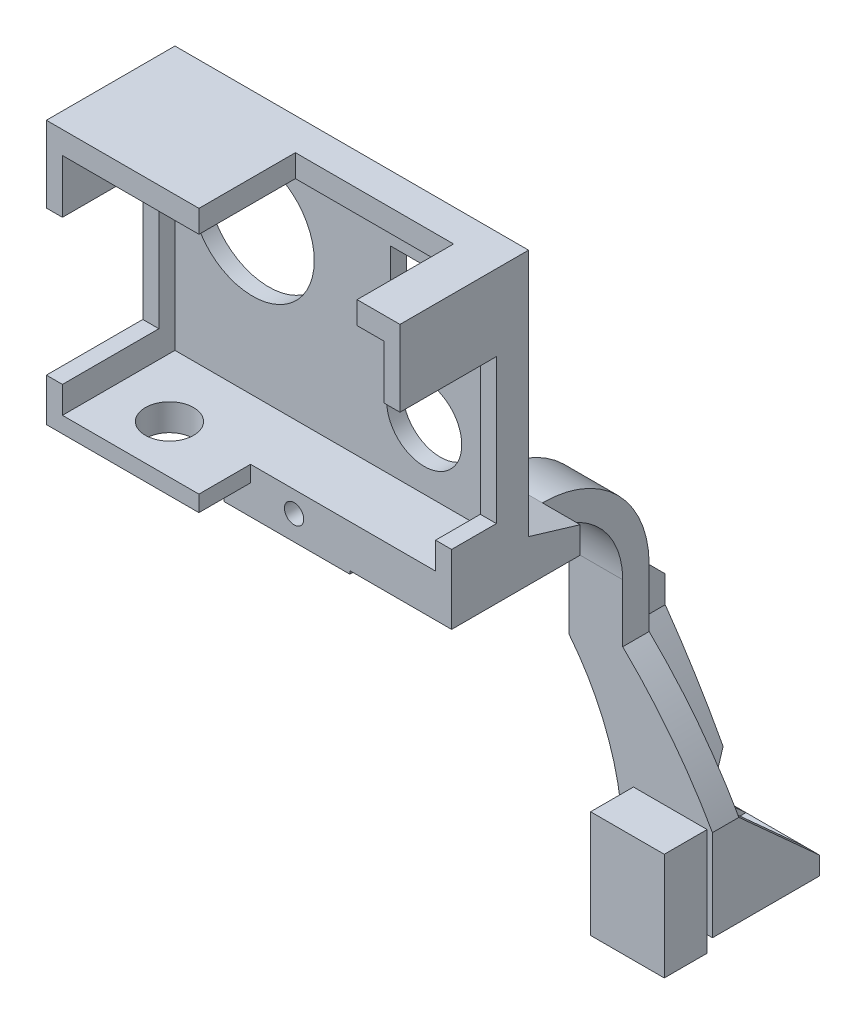
SolidWorks part; units mm, degrees
ref_plane "Plano frontal" through (0, 0, 0) normal (0, 0, 1) x (1, 0, 0)
ref_plane "Plano superior" through (0, 0, 0) normal (0, 1, 0) x (1, 0, 0)
ref_plane "Plano direito" through (0, 0, 0) normal (1, 0, 0) x (0, 0, -1)
sketch "Esboço1" plane through (0, 0, 0) normal (0, 0, 1) x (1, 0, 0)
  line L1 (0, 0) -> (-14.7, 0)
  line L3 (4.3, -61.4) -> (-14.7, -61.4)
  line L4 (-14.7, 0) -> (-14.7, -61.4)
  line L5 (0, 0) -> (4.3, -39.4)
  line L6 (4.3, -39.4) -> (4.3, -61.4)
  dimension "D1" = 14.7
  dimension "D2" = 19
  dimension "D3" = 22
  dimension "D4" = 39.4
extrude "Ressalto-extrusão1" add sketch "Esboço1" along normal blind 4.93
sketch "Esboço2" plane through (-14.7, 0, 0) normal (-1, 0, 0) x (0, 0, 1)
  line L0 (0, 0) -> (0, -61.4) construction
  line L1 (-6.1, 6.1) -> (-6.1, 11.03) construction
  line L3 (0, 0) -> (4.93, 0)
  line L4 (-6.1, 6.1) -> (-30.1, 6.1)
  line L5 (-30.1, 6.1) -> (-30.1, 11.03)
  line L6 (-30.1, 11.03) -> (-6.1, 11.03)
  arc A0 (0, 0) -> (-6.1, 6.1) centre (-6.1, 0) ccw
  arc A1 (4.93, 0) -> (-6.1, 11.03) centre (-6.1, 0) ccw
  dimension "D1" = 12.2
  dimension "D2" = 24
extrude "Ressalto-extrusão2" add sketch "Esboço2" against normal up to vertex (14.7 mm away) up to point (0, 0, 4.93)
ref_plane "Plano1" through (-12.76, 0, 0) normal (-1, 0, 0) x (0, 0, 1)
sketch "Esboço4" plane through (-12.76, 0, 0) normal (-1, 0, 0) x (0, 0, 1)
  line L0 (-30.1, 11.03) -> (-30.1, 6.1) construction
  line L1 (-30.1, 6.1) -> (-6.1, 6.1) construction
  line L2 (-6.1, 11.03) -> (-30.1, 11.03) construction
  line L3 (-45.1, -8.9) -> (-50.03, -8.9) construction
  line L4 (-30.1, 11.03) -> (-30.1, 6.1)
  line L5 (-45.1, -8.9) -> (-45.1, -61.4)
  line L6 (-45.1, -61.4) -> (-50.03, -61.4)
  line L7 (-50.03, -61.4) -> (-50.03, -8.9)
  line L8 (4.93, -61.4) -> (0, -61.4) construction
  arc A0 (-30.1, 6.1) -> (-45.1, -8.9) centre (-30.1, -8.9) ccw
  arc A1 (-30.1, 11.03) -> (-50.03, -8.9) centre (-30.1, -8.9) ccw
  dimension "D1" = 30
extrude "Ressalto-extrusão3" add sketch "Esboço4" against normal blind 10
sketch "Esboço5" plane through (0, 0, -50.03) normal (0, 0, -1) x (-1, 0, 0)
  line L0 (2.76, -8.9) -> (2.76, -61.4) construction
  line L1 (2.76, -19.73) -> (-13.99, -19.73)
  line L2 (2.76, -19.73) -> (2.76, -61.4)
  line L3 (2.76, -61.4) -> (-13.99, -61.4)
  line L4 (-13.99, -19.73) -> (-13.99, -61.4)
  line L5 (2.76, -61.4) -> (12.76, -61.4) construction
  dimension "D1" = 41.67
  dimension "D2" = 16.75
extrude "Ressalto-extrusão4" add sketch "Esboço5" against normal up to surface (4.93 mm away) up to face at (-7.76, -35.15, -45.1)
sketch "Esboço6" plane through (0, 0, -50.03) normal (0, 0, -1) x (-1, 0, 0)
  line L0 (2.76, -61.4) -> (2.76, -51.4) construction
  line L1 (12.76, -8.9) -> (12.76, -61.4) construction
  line L2 (2.76, -19.73) -> (2.76, -61.4) construction
  line L3 (-13.99, -61.4) -> (12.76, -61.4) construction
  line L4 (2.76, -19.73) -> (12.76, -19.73) construction
  line L7 (12.76, -61.4) -> (2.76, -61.4)
  line L8 (2.76, -61.4) -> (2.76, -51.4)
  line L9 (-13.99, -61.4) -> (-13.99, -41.4) construction
  line L10 (-13.99, -19.73) -> (-13.99, -61.4) construction
  line L11 (-13.99, -41.4) -> (-13.99, -19.73)
  line L12 (-13.99, -19.73) -> (2.76, -19.73)
  line L13 (12.76, -19.73) -> (12.76, -22.73)
  line L14 (12.76, -22.73) -> (12.76, -61.4)
  arc A1 (2.76, -19.73) -> (-13.99, -41.4) centre (69.0675, -88.2914) ccw
  arc A2 (12.76, -22.73) -> (2.76, -51.4) centre (48.675, -51.336) ccw
  dimension "D2" = 91.83
  dimension "D4" = 190.76
  dimension "D1" = 10
  dimension "D3" = 20
  dimension "D5" = 3
extrude "Corte-extrusão1" cut sketch "Esboço6" against normal up to next contours L14 L7 L8 A2 | L12 A1 L11
sketch "Esboço7" plane through (-2.76, 0, 0) normal (-1, 0, 0) x (0, 0, 1)
  line L0 (-50.03, -61.4) -> (-65.1, -61.4)
  line L1 (-65.1, -61.4) -> (-65.1, -55.04)
  line L2 (-65.1, -55.04) -> (-50.03, -41.4)
  line L4 (-50.03, -41.4) -> (-50.03, -61.4)
  line L5 (-45.1, -61.4) -> (-45.1, -51.4) construction
  dimension "D1" = 6.36
  dimension "D2" = 20
  dimension "D3" = 20
extrude "Ressalto-extrusão5" add sketch "Esboço7" against normal up to surface (16.75 mm away) contours L4 L0 L1 L2 up to face at (13.99, -51.4, -47.565)
sketch "Esboço8" plane through (-14.7, 0, 0) normal (-1, 0, 0) x (0, 0, 1)
  line L0 (4.93, -61.4) -> (20, -61.4)
  line L1 (20, -61.4) -> (20, -55.04)
  line L2 (20, -55.04) -> (4.93, -39.4)
  line L3 (4.93, 0) -> (4.93, -61.4) construction
  line L4 (0, 0) -> (0, -61.4) construction
  line L5 (4.93, -39.4) -> (4.93, -61.4)
  dimension "D1" = 20
  dimension "D2" = 6.36
  dimension "D3" = 22
extrude "Ressalto-extrusão6" add sketch "Esboço8" against normal up to surface (19 mm away) contours L5 L0 L1 L2 up to face at (4.3, -50.4, 2.465)
sketch "Esboço9" plane through (0, 0, -50.03) normal (0, 0, -1) x (-1, 0, 0)
  line L0 (-13.99, -41.4) -> (2.76, -41.4) construction
  line L1 (-10.99, -41.4) -> (-0.24, -41.4)
  line L2 (-10.99, -41.4) -> (-10.99, -55.04)
  line L3 (-10.99, -55.04) -> (-0.24, -55.04)
  line L4 (-0.24, -41.4) -> (-0.24, -55.04)
  line L5 (-13.99, -55.04) -> (2.76, -55.04) construction
  point P9 (-5.615, -41.4)
  point P10 (-5.615, -41.4)
  dimension "D1" = 10.75
extrude "Corte-extrusão2" cut sketch "Esboço9" along normal up to next
sketch "Esboço10" plane through (0, 0, 4.93) normal (0, 0, 1) x (1, 0, 0)
  line L0 (4.3, -39.4) -> (-14.7, -39.4) construction
  line L1 (-11.7, -39.4) -> (1.3, -39.4)
  line L2 (-11.7, -39.4) -> (-11.7, -55.04)
  line L3 (-11.7, -55.04) -> (1.3, -55.04)
  line L4 (1.3, -39.4) -> (1.3, -55.04)
  line L5 (4.3, -55.04) -> (-14.7, -55.04) construction
  point P9 (-5.2, -39.4)
  point P10 (-5.2, -39.4)
  dimension "D1" = 13
extrude "Corte-extrusão3" cut sketch "Esboço10" along normal up to next
sketch "Esboço11" plane through (0, -61.4, 0) normal (0, -1, 0) x (1, 0, 0)
  line L0 (13.99, -45.1) -> (-2.76, -45.1) construction
  line L1 (-0.76, -45.1) -> (12.99, -45.1)
  line L2 (-0.76, -45.1) -> (-0.76, -37.1)
  line L3 (-0.76, -37.1) -> (12.99, -37.1)
  line L4 (12.99, -45.1) -> (12.99, -37.1)
  line L5 (13.99, -45.1) -> (13.99, -65.1) construction
  dimension "D1" = 13.75
  dimension "D2" = 8
  dimension "D3" = 1
extrude "Ressalto-extrusão7" add sketch "Esboço11" against normal blind 20
sketch "Esboço12" plane through (0, 0, 4.93) normal (0, 0, 1) x (1, 0, 0)
  line L0 (0, 0) -> (-14.7, 0) construction
  line L1 (-10.35, 0) -> (-4.35, 0)
  line L2 (-10.35, 0) -> (-10.35, -39.4)
  line L3 (-10.35, -39.4) -> (-4.35, -39.4)
  line L4 (-4.35, 0) -> (-4.35, -39.4)
  line L5 (-11.7, -39.4) -> (-14.7, -39.4) construction
  point P9 (-7.35, 0)
  point P10 (-7.35, 0)
  dimension "D1" = 6
extrude "Ressalto-extrusão8" add sketch "Esboço12" along normal blind 5
sketch "Esboço13" plane through (0, 0, -50.03) normal (0, 0, -1) x (-1, 0, 0)
  line L0 (10.76, -8.9) -> (4.76, -8.9)
  line L1 (2.76, -8.9) -> (12.76, -8.9) construction
  line L2 (10.76, -8.9) -> (10.76, -19.73)
  line L3 (4.76, -8.9) -> (4.76, -18.9)
  line L4 (-8.615, -41.4) -> (-2.615, -41.4)
  line L5 (-10.99, -55.04) -> (-0.24, -55.04) construction
  line L6 (-13.99, -41.4) -> (-10.99, -41.4) construction
  arc A2 (10.76, -19.73) -> (-2.615, -41.4) centre (142.496, -116.0017) ccw
  arc A3 (4.76, -18.9) -> (-8.615, -41.4) centre (142.496, -116.0017) ccw
  point P5 (7.76, -8.9)
  point P6 (7.76, -8.9)
  point P13 (-5.615, -55.04)
  point P14 (-5.615, -41.4)
  dimension "D1" = 6
  dimension "D2" = 6
  dimension "D3" = 10
  dimension "D4" = 10.83
extrude "Ressalto-extrusão9" add sketch "Esboço13" along normal blind 5
chamfer "Chanfro1" distance 5 angle 45 2 edges at (-7.76, -8.9, -55.03) (5.615, -41.4, -55.03)
chamfer "Chanfro2" distance 5 angle 45 2 edges at (-7.35, -39.4, 9.93) (-7.35, 0, 9.93)
sketch "Esboço14" plane through (0, -55.04, 0) normal (0, 1, 0) x (1, 0, 0)
  line L0 (1.3, -20) -> (-11.7, -20) construction
  line L1 (10.99, 65.1) -> (0.24, 65.1) construction
  line L2 (1.3, -20) -> (1.3, -4.93) construction
  circle A0 centre (-5.2, -12.465) radius 1.6
  circle A1 centre (5.615, 57.56) radius 1.6
  point P4 (-5.2, -20)
  point P9 (5.615, 65.1)
  point P13 (1.3, -12.465)
  dimension "D1" = 3.2
  dimension "D2" = 7.54
extrude "Corte-extrusão4" cut sketch "Esboço14" against normal up to next
sketch "Esboço15" plane through (0, 11.03, 0) normal (0, 1, 0) x (1, 0, 0)
  line L0 (0, 30.1) -> (-2.76, 30.1) construction
  line L1 (-14.7, 6.1) -> (4.3, 6.1)
  line L2 (-14.7, 6.1) -> (-14.7, 30.1)
  line L3 (-14.7, 30.1) -> (4.3, 30.1)
  line L4 (4.3, 6.1) -> (4.3, 30.1)
  dimension "D1" = 19
extrude "Ressalto-extrusão10" add sketch "Esboço15" along normal blind 3 and the other way up to surface (4.93 mm away) other way up to face at (-7.4867, 6.1, -22.1)
sketch "Esboço16" plane through (0, 14.03, 0) normal (0, 1, 0) x (1, 0, 0)
  line L0 (4.3, 6.1) -> (4.3, 20.46) construction
  line L1 (4.3, 6.1) -> (4.3, 30.1) construction
  line L3 (4.3, 20.46) -> (-61.7, 20.46)
  line L4 (4.3, 20.46) -> (4.3, 17.46)
  line L5 (4.3, 17.46) -> (-61.7, 17.46)
  line L6 (-61.7, 20.46) -> (-61.7, 17.46)
  dimension "D1" = 3
  dimension "D2" = 14.36
  dimension "D3" = 66
extrude "Ressalto-extrusão11" add sketch "Esboço16" along normal blind 46.2 and the other way blind 3
sketch "Esboço17" plane through (0, 0, -17.46) normal (0, 0, 1) x (1, 0, 0)
  line L0 (-61.7, 60.23) -> (-33.22, 60.23)
  line L1 (-61.7, 60.23) -> (4.3, 60.23) construction
  line L2 (-33.22, 60.23) -> (-33.22, 56.03)
  line L3 (-33.22, 56.03) -> (-58.7, 56.03)
  line L4 (-58.7, 56.03) -> (-58.7, 46.03)
  line L5 (-58.7, 46.03) -> (-61.7, 46.03)
  line L6 (-61.7, 11.03) -> (-61.7, 60.23) construction
  line L7 (-61.7, 46.03) -> (-61.7, 60.23)
  line L15 (-61.7, 11.03) -> (-61.7, 19.03)
  line L16 (-61.7, 19.03) -> (-58.7, 19.03)
  line L17 (-58.7, 19.03) -> (-58.7, 14.03)
  line L18 (-58.7, 14.03) -> (-33.23, 14.03)
  line L19 (-33.23, 14.03) -> (-33.23, 11.03)
  line L20 (-61.7, 11.03) -> (-14.7, 11.03) construction
  line L21 (-33.23, 11.03) -> (-61.7, 11.03)
  line L22 (4.3, 60.23) -> (4.3, 46.03)
  line L23 (4.3, 14.03) -> (4.3, 60.23) construction
  line L24 (4.3, 60.23) -> (-3.7, 60.23)
  line L25 (-3.7, 60.23) -> (-3.7, 56.03)
  line L26 (-3.7, 56.03) -> (1.3, 56.03)
  line L27 (1.3, 56.03) -> (1.3, 46.03)
  line L28 (1.3, 46.03) -> (4.3, 46.03)
  dimension "D1" = 14.2
  dimension "D2" = 28.48
  dimension "D3" = 4.2
  dimension "D4" = 3
  dimension "D5" = 8
  dimension "D6" = 8
  dimension "D7" = 28.47
extrude "Ressalto-extrusão12" add sketch "Esboço17" along normal blind 21
sketch "Esboço18" plane through (0, 0, -17.46) normal (0, 0, 1) x (1, 0, 0)
  line L1 (-33.22, 60.23) -> (-3.7, 60.23)
  line L2 (-33.22, 60.23) -> (-33.22, 56.03)
  line L3 (-33.22, 56.03) -> (-3.7, 56.03)
  line L4 (-3.7, 60.23) -> (-3.7, 56.03)
  line L5 (1.3, 46.03) -> (4.3, 46.03)
  line L6 (1.3, 46.03) -> (1.3, 14.03)
  line L7 (1.3, 14.03) -> (4.3, 14.03)
  line L8 (4.3, 46.03) -> (4.3, 14.03)
  line L9 (-14.7, 14.03) -> (-33.23, 14.03)
  line L10 (-14.7, 14.03) -> (-14.7, 11.03)
  line L11 (-14.7, 11.03) -> (-33.23, 11.03)
  line L12 (-33.23, 14.03) -> (-33.23, 11.03)
  line L13 (-58.7, 19.03) -> (-61.7, 19.03)
  line L14 (-58.7, 19.03) -> (-58.7, 46.03)
  line L15 (-58.7, 46.03) -> (-61.7, 46.03)
  line L16 (-61.7, 19.03) -> (-61.7, 46.03)
extrude "Ressalto-extrusão13" add sketch "Esboço18" along normal blind 3
sketch "Esboço19" plane through (0, 0, -17.46) normal (0, 0, 1) x (1, 0, 0)
  line L0 (-58.7, 56.03) -> (1.3, 56.03) construction
  line L1 (-18.47, 51.03) -> (-6.97, 51.03)
  line L2 (-18.47, 51.03) -> (-18.47, 43.03)
  line L3 (-18.47, 43.03) -> (-6.97, 43.03)
  line L4 (-6.97, 51.03) -> (-6.97, 43.03)
  line L5 (-58.7, 14.03) -> (-58.7, 56.03) construction
  line L6 (1.3, 56.03) -> (1.3, 14.03) construction
  line L7 (1.3, 14.03) -> (-58.7, 14.03) construction
  circle A0 centre (-44.2, 41.53) radius 11.5
  circle A1 centre (-12.17, 25.53) radius 7
  dimension "D1" = 23
  dimension "D2" = 14
  dimension "D3" = 11.5
  dimension "D4" = 8
  dimension "D5" = 14.5
  dimension "D6" = 14.5
  dimension "D7" = 13.47
  dimension "D8" = 11.5
  dimension "D9" = 8.27
  dimension "D10" = 5
extrude "Corte-extrusão5" cut sketch "Esboço19" against normal up to next
chamfer "Chanfro3" distance 3 distance2 10 1 edges at (-5.2, 14.03, -30.1) first distance on face at (-6.48, 9.315, -30.1)
sketch "Esboço20" plane through (0, 11.03, 0) normal (0, -1, 0) x (1, 0, 0)
  line L0 (-61.7, 3.54) -> (-33.23, 3.54) construction
  line L1 (-61.7, -20.46) -> (-61.7, 3.54) construction
  circle A0 centre (-47.72, -5.46) radius 4.5
  dimension "D1" = 9
  dimension "D2" = 9
  dimension "D3" = 13.98
extrude "Corte-extrusão6" cut sketch "Esboço20" against normal up to next
sketch "Esboço21" plane through (0, 11.03, 0) normal (0, -1, 0) x (1, 0, 0)
  circle A0 centre (-47.72, -5.46) radius 4.5
  circle A1 centre (-47.72, -5.46) radius 4.5 construction
  circle A2 centre (-47.72, -5.46) radius 6.5
  dimension "D1" = 13
extrude "Ressalto-extrusão14" add sketch "Esboço21" along normal blind 2
ref_plane "Plano2" through (4.3, 14.03, -14.46) normal (0, 1, 0) x (1, 0, 0)
sketch "Esboço24" plane through (0, 0, -14.46) normal (0, 0, 1) x (1, 0, 0)
  line L0 (1.3, 46.03) -> (1.3, 14.03) construction
  line L1 (4.3, 14.03) -> (1.3, 14.03)
  line L2 (4.3, 14.03) -> (4.3, 19.03)
  line L3 (4.3, 19.03) -> (1.3, 19.03)
  line L4 (1.3, 14.03) -> (1.3, 19.03)
  dimension "D1" = 5
extrude "Ressalto-extrusão15" add sketch "Esboço24" along normal up to surface (8.36 mm away) up to face at (-3.4667, 10.3867, -6.1)
sketch "Esboço25" plane through (0, 11.03, 0) normal (0, -1, 0) x (1, 0, 0)
  line L0 (-14.7, -20.46) -> (-61.7, -20.46) construction
  line L1 (-30.2245, -20.46) -> (-38.2245, -20.46)
  line L2 (-30.2245, -20.46) -> (-30.2245, -14.46)
  line L3 (-30.2245, -14.46) -> (-38.2245, -14.46)
  line L4 (-38.2245, -20.46) -> (-38.2245, -14.46)
  line L5 (-30.2245, -14.46) -> (-30.2245, -20.46) construction
extrude "Ressalto-extrusão16" add sketch "Esboço25" along normal blind 5.5
sketch "Esboço26" plane through (-61.7, 0, 0) normal (-1, 0, 0) x (0, 0, 1)
  line L0 (-12.7889, 11.03) -> (-17.7888, 5.5279)
  line L1 (-12.7886, 11.0287) -> (-14.46, 19.0287) construction
  line L2 (-20.46, 11.03) -> (3.54, 11.03) construction
  line L3 (-17.7888, 5.5279) -> (-26.8765, 5.5279)
  line L4 (-26.8765, 5.5279) -> (-26.8763, 13.2729)
  line L5 (-26.8763, 13.2729) -> (-20.46, 18.2724)
  line L6 (-26.8763, 13.2729) -> (-20.46, 18.2724) construction
  line L7 (-20.46, 11.03) -> (-20.46, 60.23) construction
  line L8 (-20.46, 18.2724) -> (-20.46, 11.03)
  line L9 (-20.46, 11.03) -> (-12.7889, 11.03)
  circle A0 centre (-22.2709, 9.2979) radius 1.6
  dimension "D1" = 3.2
  dimension "D2" = 3.77
  dimension "D3" = 4.6054
extrude "Ressalto-extrusão17" add sketch "Esboço26" against normal blind 3
sketch "Esboço28" plane through (0, 0, -65.1) normal (0, 0, -1) x (-1, 0, 0)
  line L0 (2.76, -61.4) -> (2.76, -55.04) construction
  line L1 (-13.99, -61.4) -> (2.76, -61.4)
  line L2 (-13.99, -61.4) -> (-13.99, -58.4)
  line L3 (-13.99, -58.4) -> (2.76, -58.4)
  line L4 (2.76, -61.4) -> (2.76, -58.4)
  dimension "D1" = 3
extrude "Corte-extrusão7" cut sketch "Esboço28" against normal blind 20
sketch "Esboço29" plane through (0, 0, 20) normal (0, 0, 1) x (1, 0, 0)
  line L0 (4.3, -55.04) -> (4.3, -61.4) construction
  line L1 (-14.7, -61.4) -> (4.3, -61.4)
  line L2 (-14.7, -61.4) -> (-14.7, -58.4008)
  line L3 (-14.7, -58.4008) -> (4.3, -58.4008)
  line L4 (4.3, -61.4) -> (4.3, -58.4008)
  dimension "D1" = 2.9992
extrude "Corte-extrusão8" cut sketch "Esboço29" against normal blind 20
sketch "Esboço30" plane through (0, 0, -6.1) normal (0, 0, 1) x (1, 0, 0)
  line L0 (4.3, -58.4008) -> (-14.7, -58.4008) construction
  line L1 (-14.7, 14.03) -> (4.3, 14.03)
  line L2 (-14.7, 14.03) -> (-14.7, -58.4008)
  line L3 (-14.7, -58.4008) -> (4.3, -58.4008)
  line L4 (4.3, 14.03) -> (4.3, -58.4008)
  line L5 (4.3, -55.04) -> (4.3, -58.4008) construction
extrude "Corte-extrusão9" cut sketch "Esboço30" along normal through all
sketch "Esboço31" plane through (0, 0, -14.46) normal (0, 0, 1) x (1, 0, 0)
  line L1 (-38.2245, 5.53) -> (-14.7, 5.53)
  line L2 (-38.2245, 5.53) -> (-38.2245, 14.03)
  line L3 (-38.2245, 14.03) -> (-14.7, 14.03)
  line L4 (-14.7, 5.53) -> (-14.7, 14.03)
extrude "Ressalto-extrusão18" add sketch "Esboço31" along normal up to surface and the other way up to surface up to face at (-3.0333, 13.0533, -6.1) other way up to face at (-55.7, 41.53, -20.46)
sketch "Esboço32" plane through (0, 0, -6.1) normal (0, 0, 1) x (1, 0, 0)
  line L0 (-38.2245, 11.03) -> (-38.2245, 5.53) construction
  line L1 (-33.23, 14.03) -> (-58.7, 14.03) construction
  circle A0 centre (-25.11, 10.1008) radius 1.8
  dimension "D1" = 3.6
  dimension "D2" = 13.1145
  dimension "D3" = 3.9292
extrude "Corte-extrusão10" cut sketch "Esboço32" against normal blind 10
sketch "Esboço33" plane through (0, 0, -6.1) normal (0, 0, 1) x (1, 0, 0)
  line L0 (-28.26, 8.2822) -> (-28.26, 11.9195)
  line L1 (-28.26, 11.9195) -> (-25.11, 13.7381)
  line L2 (-25.11, 13.7381) -> (-21.96, 11.9195)
  line L3 (-21.96, 11.9195) -> (-21.96, 8.2822)
  line L4 (-21.96, 8.2822) -> (-25.11, 6.4635) construction
  line L5 (-25.11, 6.4635) -> (-28.26, 8.2822) construction
  line L6 (-28.26, 8.2822) -> (-28.26, 5.53)
  line L7 (-38.2245, 5.53) -> (-14.7, 5.53) construction
  line L8 (-28.26, 5.53) -> (-21.96, 5.53)
  line L9 (-21.96, 5.53) -> (-21.96, 8.2822)
  circle A0 centre (-25.11, 10.1008) radius 3.6373 construction
  point P8 (-21.96, 10.1008)
  dimension "D1" = 6.3
extrude "Corte-extrusão11" cut sketch "Esboço33" against normal blind 2.9 from offset 3 offset against normal yes
